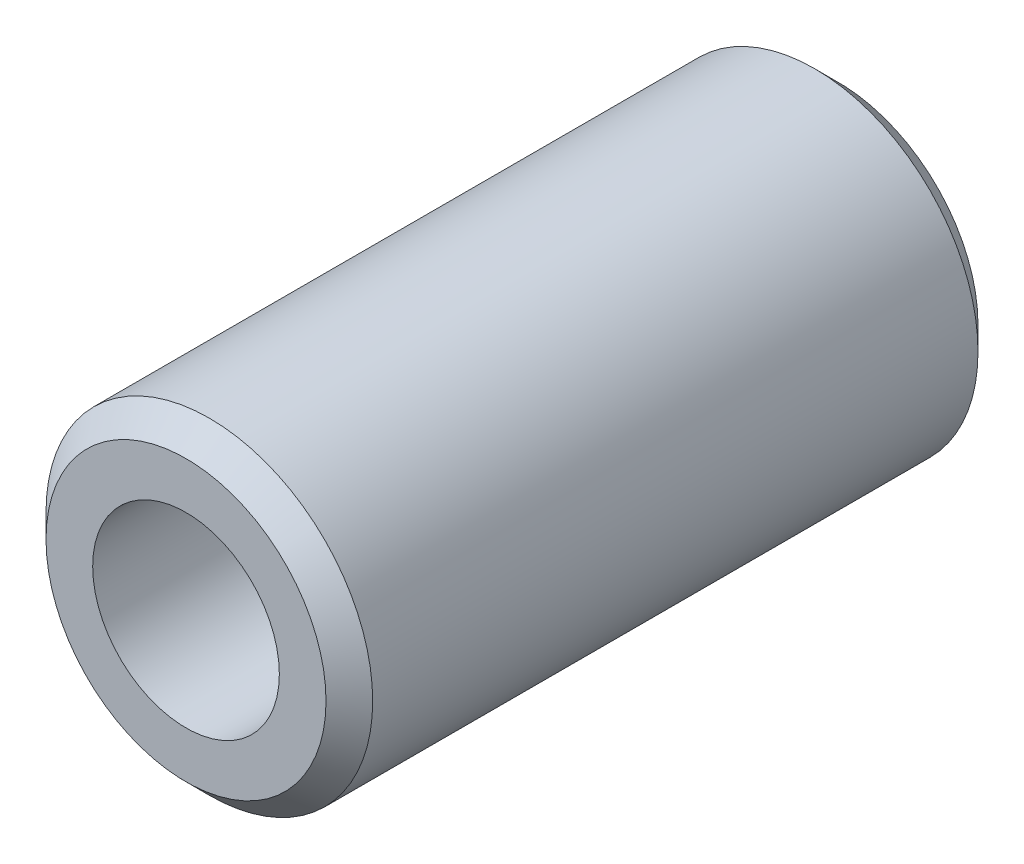
SolidWorks part; units mm, degrees
material "AISI 4340 Steel, normalized"
ref_plane "Front Plane" through (0, 0, 0) normal (0, 0, 1) x (1, 0, 0)
ref_plane "Top Plane" through (0, 0, 0) normal (0, 1, 0) x (1, 0, 0)
ref_plane "Right Plane" through (0, 0, 0) normal (1, 0, 0) x (0, 0, -1)
sketch "Sketch1" plane through (0, 0, 0) normal (0, 0, 1) x (1, 0, 0)
  circle A0 centre (0, 0) radius 17.5
  dimension "D1" = 35
extrude "Boss-Extrude1" add sketch "Sketch1" along normal blind 69.85
sketch "Sketch2" plane through (0, 0, 69.85) normal (0, 0, 1) x (1, 0, 0)
  circle A0 centre (0, 0) radius 10
  dimension "D1" = 20
extrude "Cut-Extrude1" cut sketch "Sketch2" against normal through all both and the other way through all
chamfer "Chamfer1" distance 2.5 angle 45 2 edges at (17.5, 0, 69.85) (17.5, 0, 0)
